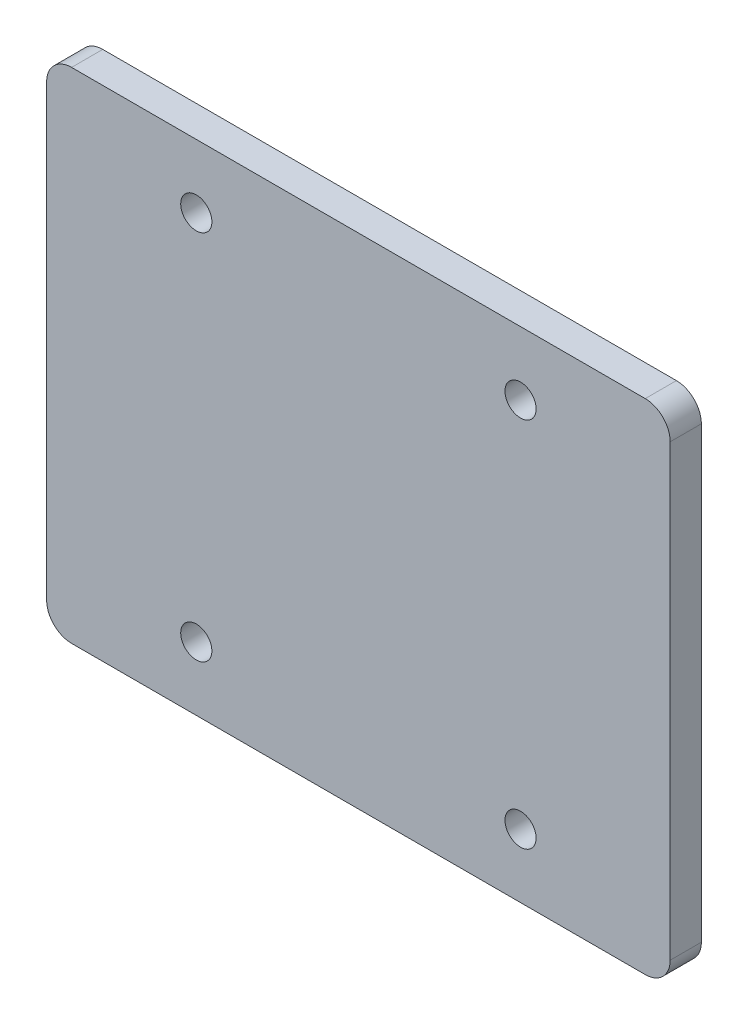
SolidWorks part; units mm, degrees
ref_plane "Front Plane" through (0, 0, 0) normal (0, 0, 1) x (1, 0, 0)
ref_plane "Top Plane" through (0, 0, 0) normal (0, 1, 0) x (1, 0, 0)
ref_plane "Right Plane" through (0, 0, 0) normal (1, 0, 0) x (0, 0, -1)
sketch "Sketch1" plane through (0, 0, 0) normal (0, 0, 1) x (1, 0, 0)
  line L1 (0, 0) -> (63.5, 0)
  line L2 (0, 0) -> (0, 50.8)
  line L3 (0, 50.8) -> (63.5, 50.8)
  line L4 (63.5, 0) -> (63.5, 50.8)
  dimension "D1" = 63.5
  dimension "D2" = 50.8
extrude "Boss-Extrude1" add sketch "Sketch1" along normal blind 3.175
fillet "Fillet1" radius 2.54 4 edges at (0, 0, 1.5875) (63.5, 0, 1.5875) (0, 50.8, 1.5875) (63.5, 50.8, 1.5875)
sketch "Sketch2" plane through (0, 0, 3.175) normal (0, 0, 1) x (1, 0, 0)
  line L0 (31.75, 0) -> (31.75, 50.8)
  line L1 (2.54, 0) -> (60.96, 0) construction
  line L2 (60.96, 50.8) -> (2.54, 50.8) construction
  line L3 (63.5, 25.4) -> (0, 25.4)
  line L4 (63.5, 2.54) -> (63.5, 48.26) construction
  line L5 (0, 48.26) -> (0, 2.54) construction
sketch "Sketch3" plane through (0, 0, 0) normal (0, 0, -1) x (-1, 0, 0)
  line L0 (0, 25.4) -> (-63.5, 25.4)
  line L1 (0, 48.26) -> (0, 2.54) construction
  line L2 (-63.5, 2.54) -> (-63.5, 48.26) construction
  line L3 (-31.75, 0) -> (-31.75, 50.8)
  line L4 (-2.54, 0) -> (-60.96, 0) construction
  line L5 (-60.96, 50.8) -> (-2.54, 50.8) construction
sketch "Sketch4" plane through (0, 0, 3.175) normal (0, 0, 1) x (1, 0, 0)
  line L0 (2.54, 0) -> (60.96, 0) construction
  line L1 (0, 48.26) -> (0, 2.54) construction
  line L2 (63.5, 25.4) -> (0, 25.4) construction
  line L3 (63.5, 2.54) -> (63.5, 48.26) construction
  line L4 (31.75, 0) -> (31.75, 50.8) construction
  line L5 (60.96, 50.8) -> (2.54, 50.8) construction
  circle A0 centre (15.24, 6.477) radius 1.5875
  circle A1 centre (15.24, 44.323) radius 1.5875
  circle A2 centre (48.26, 44.323) radius 1.5875
  circle A3 centre (48.26, 6.477) radius 1.5875
  dimension "D1" = 3.175
  dimension "D2" = 6.477
  dimension "D3" = 15.24
extrude "Cut-Extrude1" cut sketch "Sketch4" against normal up to next from surface starting at face at (31.75, 25.4, 3.175)
